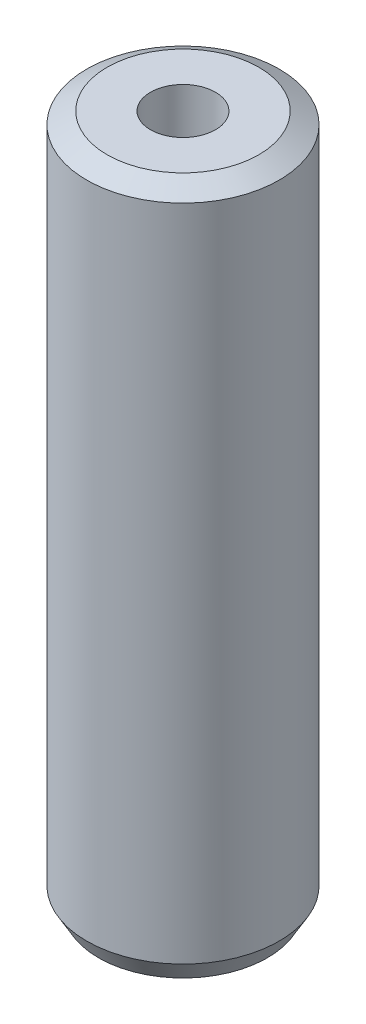
SolidWorks part; units mm, degrees
ref_plane "Front Plane" through (0, 0, 0) normal (0, 0, 1) x (1, 0, 0)
ref_plane "Top Plane" through (0, 0, 0) normal (0, 1, 0) x (1, 0, 0)
ref_plane "Right Plane" through (0, 0, 0) normal (1, 0, 0) x (0, 0, -1)
sketch "Sketch1" plane through (0, 0, 0) normal (0, 1, 0) x (1, 0, 0)
  circle A0 centre (0, 0) radius 47.5
  dimension "SHAFT_OD" = 95
extrude "Boss-Extrude1" add sketch "Sketch1" along normal blind 341.1452
sketch "Sketch2" plane through (0, 0, 0) normal (0, 1, 0) x (1, 0, 0)
  circle A0 centre (0, 0) radius 16.053
  dimension "BORE_D" = 32.1059
extrude "Cut-Extrude1" cut sketch "Sketch2" along normal through all
chamfer "Chamfer1" distance 5.8074 angle 60 2 edges at (0, 341.1452, 47.5) (0, 0, 47.5) first distance on face at (0, 341.1452, 47.5) first distance on face at (0, 0, 16.053)
